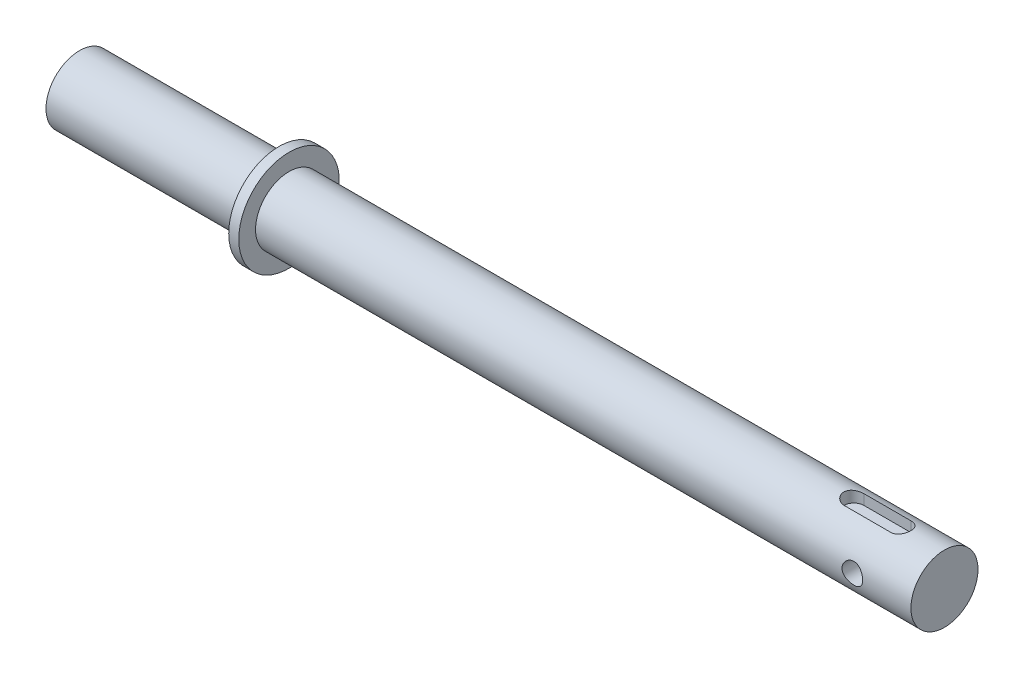
SolidWorks part; units mm, degrees
ref_plane "Alzado" through (0, 0, 0) normal (0, 0, 1) x (1, 0, 0)
ref_plane "Planta" through (0, 0, 0) normal (0, 1, 0) x (1, 0, 0)
ref_plane "Vista lateral" through (0, 0, 0) normal (1, 0, 0) x (0, 0, -1)
sketch "Croquis1" plane through (0, 0, 0) normal (1, 0, 0) x (0, 0, -1)
  circle A0 centre (0, 0) radius 10
  dimension "D1" = 20
extrude "Saliente-Extruir1" add sketch "Croquis1" along normal blind 258 from offset 8
ref_plane "Plano1" through (70.5, 0, 0) normal (-1, 0, 0) x (0, 0, 1)
sketch "Croquis2" plane through (70.5, 0, 0) normal (-1, 0, 0) x (0, 0, 1)
  circle A0 centre (0, 0) radius 15
  dimension "D1" = 30
extrude "Saliente-Extruir2" add sketch "Croquis2" along normal blind 3
sketch "Croquis3" plane through (0, 0, 0) normal (0, 0, 1) x (1, 0, 0)
  circle A0 centre (248.5, 0) radius 3.075
  dimension "D1" = 6.15
extrude "Cortar-Extruir1" cut sketch "Croquis3" against normal up to next and the other way up to next
sketch "Croquis4" plane through (0, 0, 0) normal (0, 1, 0) x (1, 0, 0)
  line L0 (266, 0) -> (231.4531, 0) construction
  line L1 (266, -10) -> (266, 10) construction
  line L2 (239, 0) -> (253, 0) construction
  line L3 (239, 3) -> (253, 3)
  line L4 (239, -3) -> (253, -3)
  arc A0 (239, 3) -> (239, -3) centre (239, 0) ccw
  arc A1 (253, -3) -> (253, 3) centre (253, 0) ccw
  point P7 (246, 0)
  dimension "D1" = 6
  dimension "D2" = 20
  dimension "D3" = 14
extrude "Cortar-Extruir2" cut sketch "Croquis4" against normal blind 3.5 from offset 10
